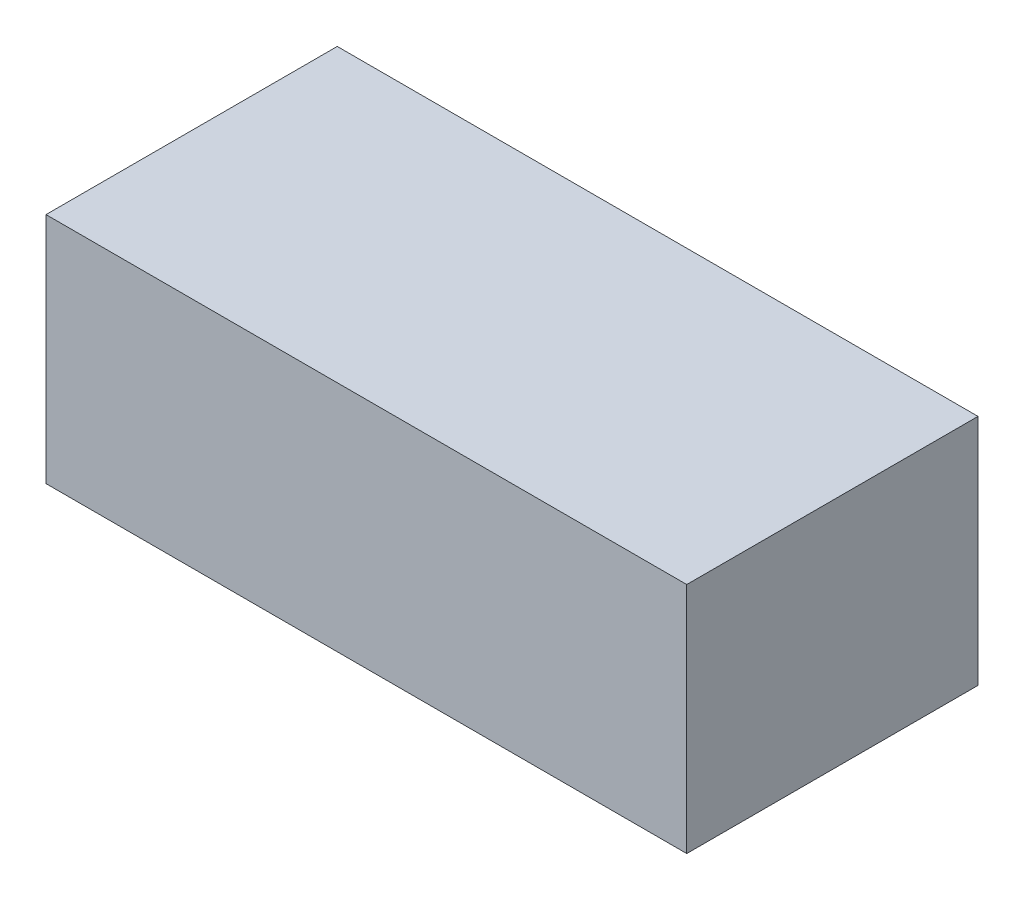
SolidWorks part; units mm, degrees
ref_plane "前视基准面" through (0, 0, 0) normal (0, 0, 1) x (1, 0, 0)
ref_plane "上视基准面" through (0, 0, 0) normal (0, 1, 0) x (1, 0, 0)
ref_plane "右视基准面" through (0, 0, 0) normal (1, 0, 0) x (0, 0, -1)
sketch "草图1" plane through (0, 0, 0) normal (0, 1, 0) x (1, 0, 0)
  line L1 (-11, 5) -> (11, 5)
  line L2 (-11, 5) -> (-11, -5)
  line L3 (-11, -5) -> (11, -5)
  line L4 (11, 5) -> (11, -5)
  line L5 (0, -5) -> (0, 5) construction
  line L6 (-11, 0) -> (11, 0) construction
  point P0 (0, 0)
  dimension "D1" = 22
  dimension "D2" = 10
extrude "凸台-拉伸1" add sketch "草图1" along normal blind 8
